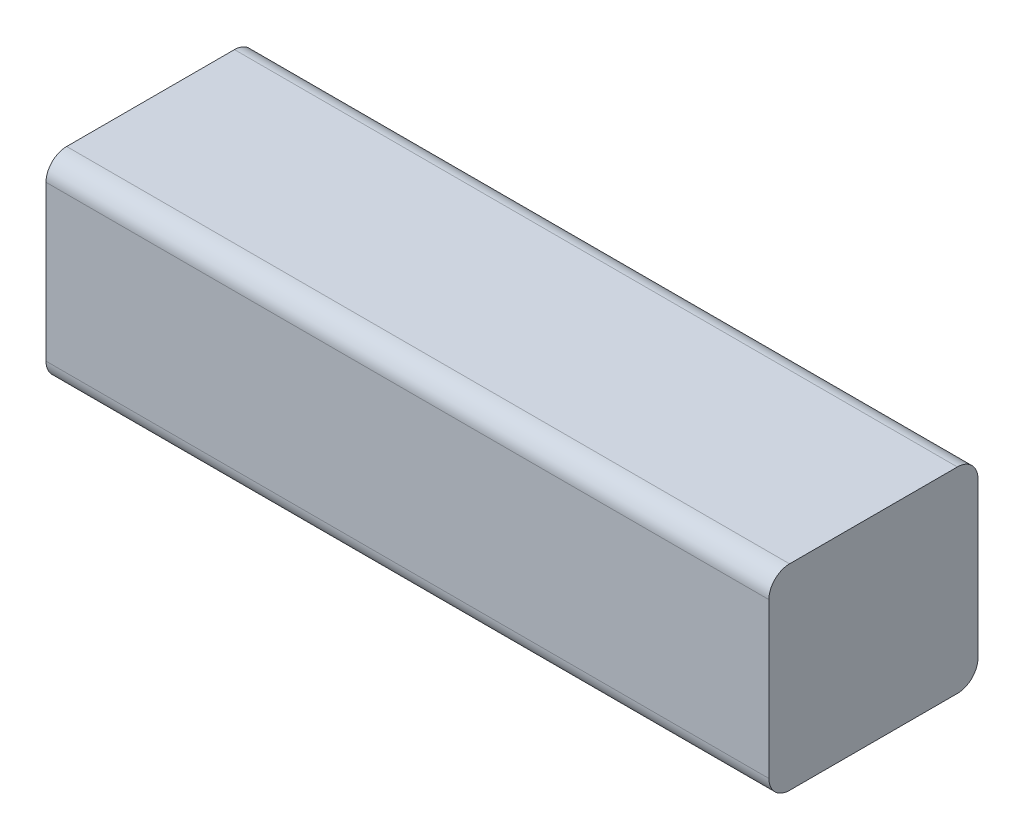
SolidWorks part; units mm, degrees
ref_plane "Front Plane" through (0, 0, 0) normal (0, 0, 1) x (1, 0, 0)
ref_plane "Top Plane" through (0, 0, 0) normal (0, 1, 0) x (1, 0, 0)
ref_plane "Right Plane" through (0, 0, 0) normal (1, 0, 0) x (0, 0, -1)
sketch "Sketch1" plane through (0, 0, 0) normal (0, 0, 1) x (1, 0, 0)
  line L1 (-273.2381, 63.7857) -> (-203.2381, 63.7857)
  line L2 (-273.2381, 63.7857) -> (-273.2381, 44.7857)
  line L3 (-273.2381, 44.7857) -> (-203.2381, 44.7857)
  line L4 (-203.2381, 63.7857) -> (-203.2381, 44.7857)
  dimension "D1" = 19
  dimension "D2" = 70
extrude "Boss-Extrude1" add sketch "Sketch1" along normal blind 20.25
fillet "Fillet1" radius 2 4 edges at (-238.2381, 63.7857, 0) (-238.2381, 44.7857, 0) (-238.2381, 44.7857, 20.25) (-238.2381, 63.7857, 20.25)
